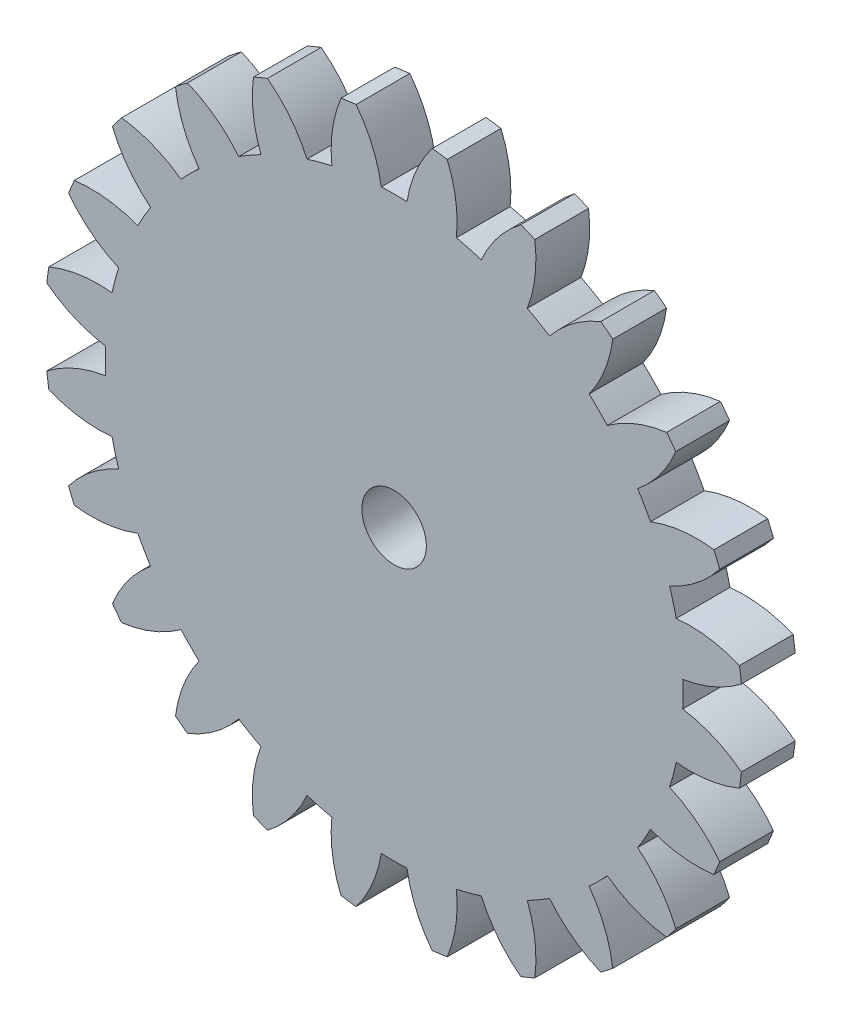
SolidWorks part; units mm, degrees
ref_plane "Front Plane" through (0, 0, 0) normal (0, 0, 1) x (1, 0, 0)
ref_plane "Top Plane" through (0, 0, 0) normal (0, 1, 0) x (1, 0, 0)
ref_plane "Right Plane" through (0, 0, 0) normal (1, 0, 0) x (0, 0, -1)
sketch "Sketch1" plane through (0, 0, 0) normal (0, 0, 1) x (1, 0, 0)
  circle A0 centre (0, 0) radius 3
  arc A96 (-32.3065, 3.5416) -> (-26.8474, 1.1963) centre (-24.9877, 13.0513) ccw
  arc A97 (-26.8474, 1.1963) -> (-26.8474, -1.1963) centre (0, 0) ccw
  arc A98 (-26.8474, -1.1963) -> (-32.3065, -3.5416) centre (-24.9877, -13.0513) ccw
  arc A99 (-32.3065, -3.5416) -> (-32.1223, -4.9406) centre (0, 0) ccw
  arc A100 (-32.1223, -4.9406) -> (-26.2422, -5.7931) centre (-27.5142, 6.1393) ccw
  arc A101 (-26.2422, -5.7931) -> (-25.6229, -8.1041) centre (0, 0) ccw
  arc A102 (-25.6229, -8.1041) -> (-30.289, -11.7824) centre (-20.7583, -19.0739) ccw
  arc A103 (-30.289, -11.7824) -> (-29.749, -13.0861) centre (0, 0) ccw
  arc A104 (-29.749, -13.0861) -> (-23.8486, -12.3877) centre (-28.1656, -1.191) ccw
  arc A105 (-23.8486, -12.3877) -> (-22.6523, -14.4597) centre (0, 0) ccw
  arc A106 (-22.6523, -14.4597) -> (-26.2074, -19.2203) centre (-15.1143, -23.7966) ccw
  arc A107 (-26.2074, -19.2203) -> (-25.3484, -20.3398) centre (0, 0) ccw
  arc A108 (-25.3484, -20.3398) -> (-19.8299, -18.138) centre (-26.8976, -8.4403) ccw
  arc A109 (-19.8299, -18.138) -> (-18.138, -19.8299) centre (0, 0) ccw
  arc A110 (-18.138, -19.8299) -> (-20.3398, -25.3484) centre (-8.4403, -26.8976) ccw
  arc A111 (-20.3398, -25.3484) -> (-19.2203, -26.2074) centre (0, 0) ccw
  arc A112 (-19.2203, -26.2074) -> (-14.4597, -22.6523) centre (-23.7966, -15.1143) ccw
  arc A113 (-14.4597, -22.6523) -> (-12.3877, -23.8486) centre (0, 0) ccw
  arc A114 (-12.3877, -23.8486) -> (-13.0861, -29.749) centre (-1.191, -28.1656) ccw
  arc A115 (-13.0861, -29.749) -> (-11.7824, -30.289) centre (0, 0) ccw
  arc A116 (-11.7824, -30.289) -> (-8.1041, -25.6229) centre (-19.0739, -20.7583) ccw
  arc A117 (-8.1041, -25.6229) -> (-5.7931, -26.2422) centre (0, 0) ccw
  arc A118 (-5.7931, -26.2422) -> (-4.9406, -32.1223) centre (6.1393, -27.5142) ccw
  arc A119 (-4.9406, -32.1223) -> (-3.5416, -32.3065) centre (0, 0) ccw
  arc A120 (-3.5416, -32.3065) -> (-1.1963, -26.8474) centre (-13.0513, -24.9877) ccw
  arc A121 (-1.1963, -26.8474) -> (1.1963, -26.8474) centre (0, 0) ccw
  arc A122 (1.1963, -26.8474) -> (3.5416, -32.3065) centre (13.0513, -24.9877) ccw
  arc A123 (3.5416, -32.3065) -> (4.9406, -32.1223) centre (0, 0) ccw
  arc A124 (4.9406, -32.1223) -> (5.7931, -26.2422) centre (-6.1393, -27.5142) ccw
  arc A125 (5.7931, -26.2422) -> (8.1041, -25.6229) centre (0, 0) ccw
  arc A126 (8.1041, -25.6229) -> (11.7824, -30.289) centre (19.0739, -20.7583) ccw
  arc A127 (11.7824, -30.289) -> (13.0861, -29.749) centre (0, 0) ccw
  arc A128 (13.0861, -29.749) -> (12.3877, -23.8486) centre (1.191, -28.1656) ccw
  arc A129 (12.3877, -23.8486) -> (14.4597, -22.6523) centre (0, 0) ccw
  arc A130 (14.4597, -22.6523) -> (19.2203, -26.2074) centre (23.7966, -15.1143) ccw
  arc A131 (19.2203, -26.2074) -> (20.3398, -25.3484) centre (0, 0) ccw
  arc A132 (20.3398, -25.3484) -> (18.138, -19.8299) centre (8.4403, -26.8976) ccw
  arc A133 (18.138, -19.8299) -> (19.8299, -18.138) centre (0, 0) ccw
  arc A134 (19.8299, -18.138) -> (25.3484, -20.3398) centre (26.8976, -8.4403) ccw
  arc A135 (25.3484, -20.3398) -> (26.2074, -19.2203) centre (0, 0) ccw
  arc A136 (26.2074, -19.2203) -> (22.6523, -14.4597) centre (15.1143, -23.7966) ccw
  arc A137 (22.6523, -14.4597) -> (23.8486, -12.3877) centre (0, 0) ccw
  arc A138 (23.8486, -12.3877) -> (29.749, -13.0861) centre (28.1656, -1.191) ccw
  arc A139 (29.749, -13.0861) -> (30.289, -11.7824) centre (0, 0) ccw
  arc A140 (30.289, -11.7824) -> (25.6229, -8.1041) centre (20.7583, -19.0739) ccw
  arc A141 (25.6229, -8.1041) -> (26.2422, -5.7931) centre (0, 0) ccw
  arc A142 (26.2422, -5.7931) -> (32.1223, -4.9406) centre (27.5142, 6.1393) ccw
  arc A143 (32.1223, -4.9406) -> (32.3065, -3.5416) centre (0, 0) ccw
  arc A144 (32.3065, -3.5416) -> (26.8474, -1.1963) centre (24.9877, -13.0513) ccw
  arc A145 (26.8474, -1.1963) -> (26.8474, 1.1963) centre (0, 0) ccw
  arc A146 (26.8474, 1.1963) -> (32.3065, 3.5416) centre (24.9877, 13.0513) ccw
  arc A147 (32.3065, 3.5416) -> (32.1223, 4.9406) centre (0, 0) ccw
  arc A148 (32.1223, 4.9406) -> (26.2422, 5.7931) centre (27.5142, -6.1393) ccw
  arc A149 (26.2422, 5.7931) -> (25.6229, 8.1041) centre (0, 0) ccw
  arc A150 (25.6229, 8.1041) -> (30.289, 11.7824) centre (20.7583, 19.0739) ccw
  arc A151 (30.289, 11.7824) -> (29.749, 13.0861) centre (0, 0) ccw
  arc A152 (29.749, 13.0861) -> (23.8486, 12.3877) centre (28.1656, 1.191) ccw
  arc A153 (23.8486, 12.3877) -> (22.6523, 14.4597) centre (0, 0) ccw
  arc A154 (22.6523, 14.4597) -> (26.2074, 19.2203) centre (15.1143, 23.7966) ccw
  arc A155 (26.2074, 19.2203) -> (25.3484, 20.3398) centre (0, 0) ccw
  arc A156 (25.3484, 20.3398) -> (19.8299, 18.138) centre (26.8976, 8.4403) ccw
  arc A157 (19.8299, 18.138) -> (18.138, 19.8299) centre (0, 0) ccw
  arc A158 (18.138, 19.8299) -> (20.3398, 25.3484) centre (8.4403, 26.8976) ccw
  arc A159 (20.3398, 25.3484) -> (19.2203, 26.2074) centre (0, 0) ccw
  arc A160 (19.2203, 26.2074) -> (14.4597, 22.6523) centre (23.7966, 15.1143) ccw
  arc A161 (14.4597, 22.6523) -> (12.3877, 23.8486) centre (0, 0) ccw
  arc A162 (12.3877, 23.8486) -> (13.0861, 29.749) centre (1.191, 28.1656) ccw
  arc A163 (13.0861, 29.749) -> (11.7824, 30.289) centre (0, 0) ccw
  arc A164 (11.7824, 30.289) -> (8.1041, 25.6229) centre (19.0739, 20.7583) ccw
  arc A165 (8.1041, 25.6229) -> (5.7931, 26.2422) centre (0, 0) ccw
  arc A166 (5.7931, 26.2422) -> (4.9406, 32.1223) centre (-6.1393, 27.5142) ccw
  arc A167 (4.9406, 32.1223) -> (3.5416, 32.3065) centre (0, 0) ccw
  arc A168 (3.5416, 32.3065) -> (1.1963, 26.8474) centre (13.0513, 24.9877) ccw
  arc A169 (1.1963, 26.8474) -> (-1.1963, 26.8474) centre (0, 0) ccw
  arc A170 (-1.1963, 26.8474) -> (-3.5416, 32.3065) centre (-13.0513, 24.9877) ccw
  arc A171 (-3.5416, 32.3065) -> (-4.9406, 32.1223) centre (0, 0) ccw
  arc A172 (-4.9406, 32.1223) -> (-5.7931, 26.2422) centre (6.1393, 27.5142) ccw
  arc A173 (-5.7931, 26.2422) -> (-8.1041, 25.6229) centre (0, 0) ccw
  arc A174 (-8.1041, 25.6229) -> (-11.7824, 30.289) centre (-19.0739, 20.7583) ccw
  arc A175 (-11.7824, 30.289) -> (-13.0861, 29.749) centre (0, 0) ccw
  arc A176 (-13.0861, 29.749) -> (-12.3877, 23.8486) centre (-1.191, 28.1656) ccw
  arc A177 (-12.3877, 23.8486) -> (-14.4597, 22.6523) centre (0, 0) ccw
  arc A178 (-14.4597, 22.6523) -> (-19.2203, 26.2074) centre (-23.7966, 15.1143) ccw
  arc A179 (-19.2203, 26.2074) -> (-20.3398, 25.3484) centre (0, 0) ccw
  arc A180 (-20.3398, 25.3484) -> (-18.138, 19.8299) centre (-8.4403, 26.8976) ccw
  arc A181 (-18.138, 19.8299) -> (-19.8299, 18.138) centre (0, 0) ccw
  arc A182 (-19.8299, 18.138) -> (-25.3484, 20.3398) centre (-26.8976, 8.4403) ccw
  arc A183 (-25.3484, 20.3398) -> (-26.2074, 19.2203) centre (0, 0) ccw
  arc A184 (-26.2074, 19.2203) -> (-22.6523, 14.4597) centre (-15.1143, 23.7966) ccw
  arc A185 (-22.6523, 14.4597) -> (-23.8486, 12.3877) centre (0, 0) ccw
  arc A186 (-23.8486, 12.3877) -> (-29.749, 13.0861) centre (-28.1656, 1.191) ccw
  arc A187 (-29.749, 13.0861) -> (-30.289, 11.7824) centre (0, 0) ccw
  arc A188 (-30.289, 11.7824) -> (-25.6229, 8.1041) centre (-20.7583, 19.0739) ccw
  arc A189 (-25.6229, 8.1041) -> (-26.2422, 5.7931) centre (0, 0) ccw
  arc A190 (-26.2422, 5.7931) -> (-32.1223, 4.9406) centre (-27.5142, -6.1393) ccw
  arc A191 (-32.1223, 4.9406) -> (-32.3065, 3.5416) centre (0, 0) ccw
  arc A192 (-32.3065, 3.5416) -> (-26.8474, 1.1963) centre (-24.9877, 13.0513) ccw
  arc A193 (-26.8474, 1.1963) -> (-26.8474, -1.1963) centre (0, 0) ccw
  arc A194 (-26.8474, -1.1963) -> (-32.3065, -3.5416) centre (-24.9877, -13.0513) ccw
  arc A195 (-32.3065, -3.5416) -> (-32.1223, -4.9406) centre (0, 0) ccw
  arc A196 (-32.1223, -4.9406) -> (-26.2422, -5.7931) centre (-27.5142, 6.1393) ccw
  arc A197 (-26.2422, -5.7931) -> (-25.6229, -8.1041) centre (0, 0) ccw
  arc A198 (-25.6229, -8.1041) -> (-30.289, -11.7824) centre (-20.7583, -19.0739) ccw
  arc A199 (-30.289, -11.7824) -> (-29.749, -13.0861) centre (0, 0) ccw
  arc A200 (-29.749, -13.0861) -> (-23.8486, -12.3877) centre (-28.1656, -1.191) ccw
  arc A201 (-23.8486, -12.3877) -> (-22.6523, -14.4597) centre (0, 0) ccw
  arc A202 (-22.6523, -14.4597) -> (-26.2074, -19.2203) centre (-15.1143, -23.7966) ccw
  arc A203 (-26.2074, -19.2203) -> (-25.3484, -20.3398) centre (0, 0) ccw
  arc A204 (-25.3484, -20.3398) -> (-19.8299, -18.138) centre (-26.8976, -8.4403) ccw
  arc A205 (-19.8299, -18.138) -> (-18.138, -19.8299) centre (0, 0) ccw
  arc A206 (-18.138, -19.8299) -> (-20.3398, -25.3484) centre (-8.4403, -26.8976) ccw
  arc A207 (-20.3398, -25.3484) -> (-19.2203, -26.2074) centre (0, 0) ccw
  arc A208 (-19.2203, -26.2074) -> (-14.4597, -22.6523) centre (-23.7966, -15.1143) ccw
  arc A209 (-14.4597, -22.6523) -> (-12.3877, -23.8486) centre (0, 0) ccw
  arc A210 (-12.3877, -23.8486) -> (-13.0861, -29.749) centre (-1.191, -28.1656) ccw
  arc A211 (-13.0861, -29.749) -> (-11.7824, -30.289) centre (0, 0) ccw
  arc A212 (-11.7824, -30.289) -> (-8.1041, -25.6229) centre (-19.0739, -20.7583) ccw
  arc A213 (-8.1041, -25.6229) -> (-5.7931, -26.2422) centre (0, 0) ccw
  arc A214 (-5.7931, -26.2422) -> (-4.9406, -32.1223) centre (6.1393, -27.5142) ccw
  arc A215 (-4.9406, -32.1223) -> (-3.5416, -32.3065) centre (0, 0) ccw
  arc A216 (-3.5416, -32.3065) -> (-1.1963, -26.8474) centre (-13.0513, -24.9877) ccw
  arc A217 (-1.1963, -26.8474) -> (1.1963, -26.8474) centre (0, 0) ccw
  arc A218 (1.1963, -26.8474) -> (3.5416, -32.3065) centre (13.0513, -24.9877) ccw
  arc A219 (3.5416, -32.3065) -> (4.9406, -32.1223) centre (0, 0) ccw
  arc A220 (4.9406, -32.1223) -> (5.7931, -26.2422) centre (-6.1393, -27.5142) ccw
  arc A221 (5.7931, -26.2422) -> (8.1041, -25.6229) centre (0, 0) ccw
  arc A222 (8.1041, -25.6229) -> (11.7824, -30.289) centre (19.0739, -20.7583) ccw
  arc A223 (11.7824, -30.289) -> (13.0861, -29.749) centre (0, 0) ccw
  arc A224 (13.0861, -29.749) -> (12.3877, -23.8486) centre (1.191, -28.1656) ccw
  arc A225 (12.3877, -23.8486) -> (14.4597, -22.6523) centre (0, 0) ccw
  arc A226 (14.4597, -22.6523) -> (19.2203, -26.2074) centre (23.7966, -15.1143) ccw
  arc A227 (19.2203, -26.2074) -> (20.3398, -25.3484) centre (0, 0) ccw
  arc A228 (20.3398, -25.3484) -> (18.138, -19.8299) centre (8.4403, -26.8976) ccw
  arc A229 (18.138, -19.8299) -> (19.8299, -18.138) centre (0, 0) ccw
  arc A230 (19.8299, -18.138) -> (25.3484, -20.3398) centre (26.8976, -8.4403) ccw
  arc A231 (25.3484, -20.3398) -> (26.2074, -19.2203) centre (0, 0) ccw
  arc A232 (26.2074, -19.2203) -> (22.6523, -14.4597) centre (15.1143, -23.7966) ccw
  arc A233 (22.6523, -14.4597) -> (23.8486, -12.3877) centre (0, 0) ccw
  arc A234 (23.8486, -12.3877) -> (29.749, -13.0861) centre (28.1656, -1.191) ccw
  arc A235 (29.749, -13.0861) -> (30.289, -11.7824) centre (0, 0) ccw
  arc A236 (30.289, -11.7824) -> (25.6229, -8.1041) centre (20.7583, -19.0739) ccw
  arc A237 (25.6229, -8.1041) -> (26.2422, -5.7931) centre (0, 0) ccw
  arc A238 (26.2422, -5.7931) -> (32.1223, -4.9406) centre (27.5142, 6.1393) ccw
  arc A239 (32.1223, -4.9406) -> (32.3065, -3.5416) centre (0, 0) ccw
  arc A240 (32.3065, -3.5416) -> (26.8474, -1.1963) centre (24.9877, -13.0513) ccw
  arc A241 (26.8474, -1.1963) -> (26.8474, 1.1963) centre (0, 0) ccw
  arc A242 (26.8474, 1.1963) -> (32.3065, 3.5416) centre (24.9877, 13.0513) ccw
  arc A243 (32.3065, 3.5416) -> (32.1223, 4.9406) centre (0, 0) ccw
  arc A244 (32.1223, 4.9406) -> (26.2422, 5.7931) centre (27.5142, -6.1393) ccw
  arc A245 (26.2422, 5.7931) -> (25.6229, 8.1041) centre (0, 0) ccw
  arc A246 (25.6229, 8.1041) -> (30.289, 11.7824) centre (20.7583, 19.0739) ccw
  arc A247 (30.289, 11.7824) -> (29.749, 13.0861) centre (0, 0) ccw
  arc A248 (29.749, 13.0861) -> (23.8486, 12.3877) centre (28.1656, 1.191) ccw
  arc A249 (23.8486, 12.3877) -> (22.6523, 14.4597) centre (0, 0) ccw
  arc A250 (22.6523, 14.4597) -> (26.2074, 19.2203) centre (15.1143, 23.7966) ccw
  arc A251 (26.2074, 19.2203) -> (25.3484, 20.3398) centre (0, 0) ccw
  arc A252 (25.3484, 20.3398) -> (19.8299, 18.138) centre (26.8976, 8.4403) ccw
  arc A253 (19.8299, 18.138) -> (18.138, 19.8299) centre (0, 0) ccw
  arc A254 (18.138, 19.8299) -> (20.3398, 25.3484) centre (8.4403, 26.8976) ccw
  arc A255 (20.3398, 25.3484) -> (19.2203, 26.2074) centre (0, 0) ccw
  arc A256 (19.2203, 26.2074) -> (14.4597, 22.6523) centre (23.7966, 15.1143) ccw
  arc A257 (14.4597, 22.6523) -> (12.3877, 23.8486) centre (0, 0) ccw
  arc A258 (12.3877, 23.8486) -> (13.0861, 29.749) centre (1.191, 28.1656) ccw
  arc A259 (13.0861, 29.749) -> (11.7824, 30.289) centre (0, 0) ccw
  arc A260 (11.7824, 30.289) -> (8.1041, 25.6229) centre (19.0739, 20.7583) ccw
  arc A261 (8.1041, 25.6229) -> (5.7931, 26.2422) centre (0, 0) ccw
  arc A262 (5.7931, 26.2422) -> (4.9406, 32.1223) centre (-6.1393, 27.5142) ccw
  arc A263 (4.9406, 32.1223) -> (3.5416, 32.3065) centre (0, 0) ccw
  arc A264 (3.5416, 32.3065) -> (1.1963, 26.8474) centre (13.0513, 24.9877) ccw
  arc A265 (1.1963, 26.8474) -> (-1.1963, 26.8474) centre (0, 0) ccw
  arc A266 (-1.1963, 26.8474) -> (-3.5416, 32.3065) centre (-13.0513, 24.9877) ccw
  arc A267 (-3.5416, 32.3065) -> (-4.9406, 32.1223) centre (0, 0) ccw
  arc A268 (-4.9406, 32.1223) -> (-5.7931, 26.2422) centre (6.1393, 27.5142) ccw
  arc A269 (-5.7931, 26.2422) -> (-8.1041, 25.6229) centre (0, 0) ccw
  arc A270 (-8.1041, 25.6229) -> (-11.7824, 30.289) centre (-19.0739, 20.7583) ccw
  arc A271 (-11.7824, 30.289) -> (-13.0861, 29.749) centre (0, 0) ccw
  arc A272 (-13.0861, 29.749) -> (-12.3877, 23.8486) centre (-1.191, 28.1656) ccw
  arc A273 (-12.3877, 23.8486) -> (-14.4597, 22.6523) centre (0, 0) ccw
  arc A274 (-14.4597, 22.6523) -> (-19.2203, 26.2074) centre (-23.7966, 15.1143) ccw
  arc A275 (-19.2203, 26.2074) -> (-20.3398, 25.3484) centre (0, 0) ccw
  arc A276 (-20.3398, 25.3484) -> (-18.138, 19.8299) centre (-8.4403, 26.8976) ccw
  arc A277 (-18.138, 19.8299) -> (-19.8299, 18.138) centre (0, 0) ccw
  arc A278 (-19.8299, 18.138) -> (-25.3484, 20.3398) centre (-26.8976, 8.4403) ccw
  arc A279 (-25.3484, 20.3398) -> (-26.2074, 19.2203) centre (0, 0) ccw
  arc A280 (-26.2074, 19.2203) -> (-22.6523, 14.4597) centre (-15.1143, 23.7966) ccw
  arc A281 (-22.6523, 14.4597) -> (-23.8486, 12.3877) centre (0, 0) ccw
  arc A282 (-23.8486, 12.3877) -> (-29.749, 13.0861) centre (-28.1656, 1.191) ccw
  arc A283 (-29.749, 13.0861) -> (-30.289, 11.7824) centre (0, 0) ccw
  arc A284 (-30.289, 11.7824) -> (-25.6229, 8.1041) centre (-20.7583, 19.0739) ccw
  arc A285 (-25.6229, 8.1041) -> (-26.2422, 5.7931) centre (0, 0) ccw
  arc A286 (-26.2422, 5.7931) -> (-32.1223, 4.9406) centre (-27.5142, -6.1393) ccw
  arc A287 (-32.1223, 4.9406) -> (-32.3065, 3.5416) centre (0, 0) ccw
  dimension "D1" = 0
extrude "Boss-Extrude1" add sketch "Sketch1" along normal blind 5 contours A0 | A192 A193 A194 A195 A196 A197 A198 A199 A200 A201 A202 A203 A204 A205 A206 A207 A208 A209 A210 A211 A212 A213 A214 A215 A216 A217 A218 A219 A220 A221 A222 A223 A224 A225 A226 A227 A228 A229 A230 A231 A232 A233 A234 A235 A236 A237 A238 A239 A240 A241 A242 A243 A244 A245 A246 A247 A248 A249 A250 A251 A252 A253 A254 A255 A256 A257 A258 A259 A260 A261 A262 A263 A264 A265 A266 A267 A268 A269 A270 A271 A272 A273 A274 A275 A276 A277 A278 A279 A280 A281 A282 A283 A284 A285 A286 A287 region at (0, 0, 0)
